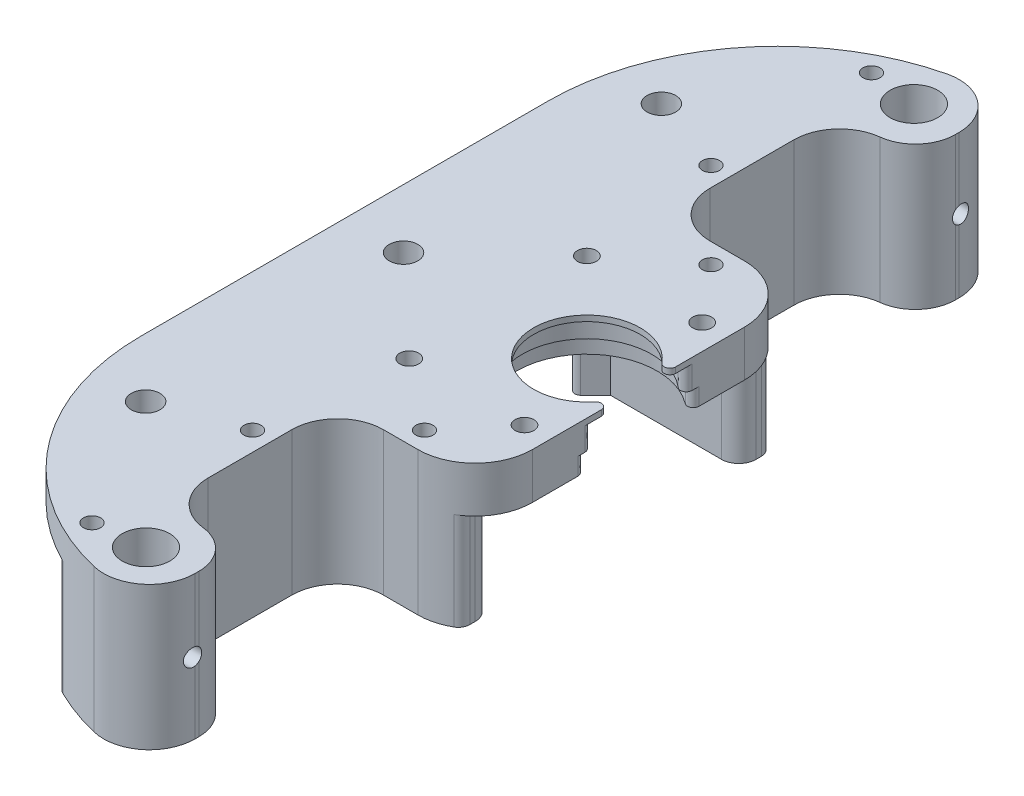
SolidWorks part; units mm, degrees
material "ABS"
ref_plane "Płaszczyzna przednia" through (0, 0, 0) normal (0, 0, 1) x (1, 0, 0)
ref_plane "Płaszczyzna górna" through (0, 0, 0) normal (0, 1, 0) x (1, 0, 0)
ref_plane "Płaszczyzna prawa" through (0, 0, 0) normal (1, 0, 0) x (0, 0, -1)
sketch "Szkic2" plane through (0, 0, 0) normal (0, 1, 0) x (1, 0, 0)
  line L0 (-29.6604, 52.1749) -> (-33.4767, 55.9912) construction
  line L1 (-33.4767, 55.9912) -> (-67.8442, 55.9912) construction
  line L2 (-67.8442, 55.9912) -> (-71.6604, 52.1749) construction
  line L3 (-71.6604, 52.1749) -> (-71.6604, 17.8074) construction
  line L4 (-71.6604, 17.8074) -> (-67.8442, 13.9912) construction
  line L5 (-67.8442, 13.9912) -> (-33.4767, 13.9912) construction
  line L6 (-33.4767, 13.9912) -> (-29.6604, 17.8074) construction
  line L7 (-29.6604, 17.8074) -> (-29.6604, 52.1749) construction
  line L8 (-50.6604, 34.9912) -> (-92.6604, 34.9912) construction
  line L9 (-72.3604, -11.5088) -> (-92.9604, -11.5088) construction
  line L10 (-65.6604, 13.4912) -> (-33.2696, 13.4912)
  line L11 (-33.2696, 13.4912) -> (-29.1604, 17.6003) construction
  line L12 (-29.1604, 17.6003) -> (-29.1604, 52.382)
  line L13 (-29.1604, 52.382) -> (-33.2696, 56.4912) construction
  line L14 (-33.2696, 56.4912) -> (-65.6604, 56.4912)
  line L15 (-65.6604, 81.4912) -> (-33.2696, 56.4912)
  line L16 (-72.3604, 17.8003) -> (-72.3604, -11.5088)
  line L17 (-92.9604, -11.5088) -> (-92.9604, 81.4912)
  line L18 (-69.0104, 109.9912) -> (-69.0104, 102.9912) construction
  line L19 (-65.6604, -11.5088) -> (-65.6604, 13.4912)
  line L20 (-65.6604, -11.5088) -> (-33.2696, 13.4912)
  line L21 (-33.2696, 13.4912) -> (-29.1604, 13.4912)
  line L22 (-29.1604, 13.4912) -> (-29.1604, 17.6003)
  line L23 (-29.1604, 52.382) -> (-29.1604, 56.4912)
  line L24 (-29.1604, 56.4912) -> (-33.2696, 56.4912)
  line L25 (-68.0513, 13.4912) -> (-72.3604, 17.8003)
  line L26 (-68.0513, 56.4912) -> (-72.3604, 52.182)
  line L27 (-65.6604, 81.4912) -> (-65.6604, 56.4912)
  line L28 (-92.9604, 81.4912) -> (-92.9604, 109.9912)
  line L29 (-72.3604, 52.182) -> (-72.3604, 81.4912)
  line L30 (-72.3604, 81.4912) -> (-92.9604, 81.4912) construction
  line L31 (-65.6604, 13.4912) -> (-68.0513, 13.4912)
  line L32 (-68.0513, 56.4912) -> (-65.6604, 56.4912)
  line L33 (-82.6604, -11.5088) -> (-82.6604, 81.4912) construction
  line L34 (-65.6604, 13.4912) -> (-65.6604, 6.4912)
  line L35 (-65.6604, 6.4912) -> (-45.6604, 6.4912)
  line L36 (-45.6604, 6.4912) -> (-45.6604, 13.4912)
  line L37 (-45.6604, 13.4912) -> (-65.6604, 13.4912)
  line L38 (-65.6604, 63.4912) -> (-45.6604, 63.4912)
  line L39 (-45.6604, 63.4912) -> (-45.6604, 56.4912)
  line L40 (-65.6604, 56.4912) -> (-65.6604, 63.4912)
  line L41 (-45.6604, 56.4912) -> (-65.6604, 56.4912)
  line L42 (-92.9604, 109.9912) -> (-72.3604, 109.9912)
  line L43 (-92.9604, -11.5088) -> (-92.9604, -40.0088)
  line L44 (-65.6604, 81.4912) -> (-65.6604, 109.9912)
  line L45 (-69.0104, -40.0088) -> (-69.0104, 109.9912) construction
  line L46 (-45.6604, 9.9912) -> (-72.3604, 9.9912) construction
  line L47 (-45.6604, 59.9912) -> (-72.3604, 59.9912) construction
  line L48 (-72.3604, 109.9912) -> (-52.3604, 109.9912)
  line L49 (-52.3604, -40.0088) -> (-52.3604, 13.4912)
  line L50 (-72.3604, -40.0088) -> (-52.3604, -40.0088)
  line L51 (-72.3604, 109.9912) -> (-72.3604, -40.0088)
  line L52 (-65.6604, 109.9912) -> (-72.3604, 109.9912)
  line L53 (-72.3604, -11.5088) -> (-72.3604, -40.0088)
  line L54 (-65.6604, -40.0088) -> (-65.6604, -11.5088)
  line L55 (-92.9604, -40.0088) -> (-72.3604, -40.0088)
  line L56 (-52.3604, 56.4912) -> (-52.3604, 109.9912)
  circle A0 centre (-50.6604, 34.9912) radius 11.75 construction
  circle A1 centre (-66.1604, 50.4912) radius 1.5 construction
  circle A2 centre (-35.1604, 50.4912) radius 1.5 construction
  circle A3 centre (-35.1604, 19.4912) radius 1.5 construction
  circle A4 centre (-66.1604, 19.4912) radius 1.5 construction
  circle A5 centre (-50.6604, 34.9912) radius 4 construction
  circle A6 centre (-50.6604, 34.9912) radius 11 construction
  circle A7 centre (-82.6604, 34.9912) radius 2.5
  circle A8 centre (-82.6604, -10.0088) radius 2.5
  circle A9 centre (-82.6604, 79.9912) radius 2.5
  circle A10 centre (-50.6604, 34.9912) radius 12.25 construction
  circle A11 centre (-66.1604, 19.4912) radius 1.65
  circle A12 centre (-66.1604, 50.4912) radius 1.65
  circle A13 centre (-35.1604, 50.4912) radius 1.65
  circle A14 centre (-35.1604, 19.4912) radius 1.65
  circle A15 centre (-69.0104, 9.9912) radius 1.5 construction
  circle A16 centre (-69.0104, 102.9912) radius 1.5
  circle A17 centre (-69.0104, -33.0088) radius 1.5
  circle A18 centre (-46.0512, 19.4912) radius 1.65
  circle A19 centre (-46.0512, 50.4912) radius 1.65
  circle A23 centre (-54.0104, 9.9912) radius 1.5
  circle A24 centre (-69.0104, -5.0088) radius 1.5
  circle A25 centre (-54.0104, 59.9912) radius 1.5
  circle A26 centre (-69.0104, 74.9912) radius 1.5
  circle A27 centre (-69.0104, 59.9912) radius 1.5 construction
  circle A28 centre (-50.6604, 34.9912) radius 11.3
  circle A29 centre (-60.5945, -32.0088) radius 4.15
  circle A30 centre (-60.5945, 101.9912) radius 4.15
  point P40 (-92.9604, 34.9912)
  point P66 (-92.9604, 34.9912)
  dimension "D1" = 45
  dimension "D2" = 7
extrude "Dodanie-wyciągnięcie1" add sketch "Szkic2" along normal blind 5 contours L26 L51 L25 L31 L10 L37 L21 L22 L12 L23 L24 L14 L41 L32 A28 A14 A13 A12 A11 | L43 L55 L51 L16 L29 L42 L28 L17 A8 A9 | L50 L54 L19 L31 L25 L16 L51 A24 | L35 L49 L10 L19 A23 | L49 L35 L36 L37 | L20 L49 L35 L19 | L54 L50 L49 L20 A29 | L49 L20 L10 L36 L35 | L48 L51 L29 L26 L32 L27 L44 A16 A26 | L38 L56 L15 L27 | L15 L56 L48 L44 A30 | L41 L56 L38 L27 A25 | L56 L14 L39 L38 | L56 L38 L39 L14 L15 region at (-66.8559, 0, -14.1007) region at (-59.4213, 0, -9.9912) region at (-69.0607, 0, 12.2889) region at (-49.0104, 0, -9.9912) region at (-59.8946, 0, 0.2837) region at (-44.4892, 0, -7.8734) region at (-58.4076, 0, 21.8309) region at (-73.8745, 0, -3.1457) region at (-69.0607, 0, -82.2712) region at (-59.4213, 0, -59.9912) region at (-49.0104, 0, -59.9912) region at (-59.8946, 0, -70.2661) region at (-58.4076, 0, -91.8132) region at (-44.4892, 0, -62.1089)
extrude "Dodanie-wyciągnięcie2" add sketch "Szkic2<3>" against normal blind 20 contours L49 L35 L36 L37 | L35 L49 L10 L19 A23 | L50 L54 L19 L31 L25 L16 L51 A24 | L48 L51 L29 L26 L32 L27 L44 A16 A26 | L41 L56 L38 L27 A25 | L56 L14 L39 L38 region at (-59.4213, 0, -9.9912) region at (-69.0607, 0, 12.2889) region at (-49.0104, 0, -9.9912) region at (-69.0607, 0, -82.2712) region at (-59.4213, 0, -59.9912) region at (-49.0104, 0, -59.9912)
sketch "Szkic2<3>" plane through (0, 0, 0) normal (0, 1, 0) x (1, 0, 0) same geometry as "Szkic2"
fillet "Zaokrąglenie1" radius 7 2 edges at (-52.3604, 2.5, -109.9912) (-52.3604, 2.5, 40.0088)
sketch "Szkic3" plane through (0, 0, 0) normal (0, -1, 0) x (1, 0, 0)
  line L0 (-65.6604, -109.9912) -> (-59.3604, -109.9912) construction
  line L1 (-65.6604, 40.0088) -> (-59.3604, 40.0088) construction
  line L2 (-65.6604, -109.9912) -> (-59.3604, -109.9912)
  line L3 (-65.6604, 40.0088) -> (-59.3604, 40.0088)
  line L4 (-65.6604, 24.0088) -> (-59.3604, 24.0088)
  line L5 (-56.4445, 32.0088) -> (-64.7445, 32.0088) construction
  line L6 (-56.4445, -101.9912) -> (-64.7445, -101.9912) construction
  line L7 (-65.6604, -93.9912) -> (-59.3604, -93.9912)
  line L8 (-52.3604, 33.0088) -> (-52.3604, 31.0088)
  line L9 (-65.6604, 40.0088) -> (-65.6604, 24.0088)
  line L10 (-52.3604, -100.9912) -> (-52.3604, -102.9912)
  line L11 (-65.6604, -93.9912) -> (-65.6604, -109.9912)
  arc A0 (-59.3604, -109.9912) -> (-52.3604, -102.9912) centre (-59.3604, -102.9912) ccw construction
  arc A1 (-52.3604, 33.0088) -> (-59.3604, 40.0088) centre (-59.3604, 33.0088) ccw construction
  arc A2 (-59.3604, -109.9912) -> (-52.3604, -102.9912) centre (-59.3604, -102.9912) ccw
  arc A3 (-52.3604, 33.0088) -> (-59.3604, 40.0088) centre (-59.3604, 33.0088) ccw
  circle A4 centre (-60.5945, 32.0088) radius 4.15 construction
  circle A5 centre (-60.5945, -101.9912) radius 4.15 construction
  arc A6 (-52.3604, 31.0088) -> (-59.3604, 24.0088) centre (-59.3604, 31.0088) cw
  arc A7 (-59.3604, -93.9912) -> (-52.3604, -100.9912) centre (-59.3604, -100.9912) cw
  circle A8 centre (-60.5945, 32.0088) radius 4.15
  circle A9 centre (-60.5945, -101.9912) radius 4.15
extrude "Dodanie-wyciągnięcie3" add sketch "Szkic3" along normal up to surface (20 mm away) up to face at (-62.202, -20, 3.1789)
fillet "Zaokrąglenie2" radius 3 4 edges at (-45.6604, -10, -63.4912) (-45.6604, -10, -56.4912) (-45.6604, -10, -13.4912) (-45.6604, -10, -6.4912)
fillet "Zaokrąglenie3" radius 10 2 edges at (-33.2696, 2.5, -56.4912) (-33.2696, 2.5, -13.4912)
sketch "Szkic4" plane through (0, 0, 0) normal (0, -1, 0) x (1, 0, 0)
  line L1 (-52.3604, 31.0088) -> (-52.3604, 1.2436) construction
  line L4 (-65.6604, -6.4912) -> (-48.6604, -6.4912) construction
  line L5 (-52.3604, 31.0088) -> (-52.3604, 1.2436)
  line L6 (-65.6604, 24.0088) -> (-65.6604, -6.4912) construction
  line L7 (-65.6604, 24.0088) -> (-59.3604, 24.0088) construction
  line L8 (-52.3604, -71.2259) -> (-52.3604, -100.9912) construction
  line L9 (-59.3604, -93.9912) -> (-65.6604, -93.9912) construction
  line L12 (-52.3604, -71.2259) -> (-52.3604, -100.9912)
  line L13 (-59.3604, -93.9912) -> (-65.6604, -93.9912)
  line L14 (-65.6604, -63.4912) -> (-48.6604, -63.4912) construction
  line L15 (-65.6604, -93.9912) -> (-65.6604, -63.4912) construction
  line L16 (-48.6604, -63.4912) -> (-42.339, -63.4912)
  line L17 (-52.3604, -71.2259) -> (-35.9693, -58.5749) construction
  line L18 (-42.339, -63.4912) -> (-52.3604, -71.2259)
  line L19 (-48.6604, -6.4912) -> (-42.339, -6.4912)
  line L20 (-52.3604, 1.2436) -> (-35.9693, -11.4075) construction
  line L21 (-42.339, -6.4912) -> (-52.3604, 1.2436)
  line L22 (-65.6604, -93.9912) -> (-65.6604, -63.4912)
  line L23 (-65.6604, -63.4912) -> (-48.6604, -63.4912)
  line L24 (-65.6604, 24.0088) -> (-59.3604, 24.0088)
  line L25 (-65.6604, 24.0088) -> (-65.6604, -6.4912)
  line L26 (-65.6604, -6.4912) -> (-48.6604, -6.4912)
  arc A2 (-59.3604, 24.0088) -> (-52.3604, 31.0088) centre (-59.3604, 31.0088) ccw construction
  arc A5 (-59.3604, 24.0088) -> (-52.3604, 31.0088) centre (-59.3604, 31.0088) ccw
  arc A6 (-52.3604, -100.9912) -> (-59.3604, -93.9912) centre (-59.3604, -100.9912) ccw construction
  arc A9 (-52.3604, -100.9912) -> (-59.3604, -93.9912) centre (-59.3604, -100.9912) ccw
extrude "Wytnij-wyciągnięcie1" cut sketch "Szkic4" against normal through all
fillet "Zaokrąglenie4" radius 15 4 edges at (-29.1604, 2.5, -56.4912) (-29.1604, 2.5, -13.4912) (-42.339, 2.5, -63.4912) (-42.339, 2.5, -6.4912)
fillet "Zaokrąglenie5" radius 1 2 edges at (-72.3604, -10, -52.182) (-72.3604, -10, -17.8003)
fillet "Zaokrąglenie6" radius 40 2 edges at (-92.9604, 2.5, -109.9912) (-92.9604, 2.5, 40.0088)
fillet "Zaokrąglenie7" radius 3 2 edges at (-72.3604, -10, -105.4871) (-72.3604, -10, 35.5047)
fillet "Zaokrąglenie10" radius 8 2 edges at (-59.3604, -7.5, -109.9912) (-59.3604, -7.5, 40.0088)
fillet "Zaokrąglenie11" radius 8 4 edges at (-65.6604, -7.5, 24.0088) (-65.6604, -7.5, -93.9912) (-65.6604, -7.5, -63.4912) (-65.6604, -7.5, -6.4912)
sketch "Szkic6" plane through (0, 5, 0) normal (0, 1, 0) x (1, 0, 0)
  circle A0 centre (-50.6604, 34.9912) radius 11.3 construction
  circle A1 centre (-50.6604, 34.9912) radius 11.3
  circle A2 centre (-50.6604, 34.9912) radius 9.3
  dimension "D1" = 2
extrude "Dodanie-wyciągnięcie4" add sketch "Szkic6" against normal blind 1
sketch "Szkic7" plane through (0, 0, 0) normal (0, -1, 0) x (1, 0, 0)
  line L0 (-72.3604, -15.3861) -> (-72.3604, -54.5963)
  line L14 (-92.9604, 0.5241) -> (-92.9604, -70.5065)
  line L15 (-72.3604, -103.6733) -> (-72.3604, -54.5963)
  line L16 (-70.6533, -53.8892) -> (-68.0513, -56.4912)
  line L17 (-68.0513, -56.4912) -> (-48.6604, -56.4912)
  line L18 (-45.6604, -59.4912) -> (-45.6604, -60.4912)
  line L19 (-48.6604, -63.4912) -> (-47.4545, -63.4912)
  line L20 (-38.2895, -60.3656) -> (-35.9693, -58.5749)
  line L21 (-29.1604, -45.9856) -> (-29.1604, -23.9967)
  line L22 (-35.9693, -11.4075) -> (-38.2895, -9.6167)
  line L23 (-47.4545, -6.4912) -> (-48.6604, -6.4912)
  line L24 (-45.6604, -9.4912) -> (-45.6604, -10.4912)
  line L25 (-48.6604, -13.4912) -> (-68.0513, -13.4912)
  line L26 (-68.0513, -13.4912) -> (-70.6533, -16.0932)
  line L27 (-72.3604, -15.3861) -> (-72.3604, 33.691)
  line L30 (-70.6533, -53.8892) -> (-68.0513, -56.4912)
  line L31 (-68.0513, -56.4912) -> (-48.6604, -56.4912)
  line L32 (-45.6604, -59.4912) -> (-45.6604, -60.4912)
  line L33 (-48.6604, -63.4912) -> (-47.4545, -63.4912)
  line L34 (-38.2895, -60.3656) -> (-35.9693, -58.5749)
  line L35 (-29.1604, -45.9856) -> (-29.1604, -23.9967)
  line L36 (-35.9693, -11.4075) -> (-38.2895, -9.6167)
  line L37 (-47.4545, -6.4912) -> (-48.6604, -6.4912)
  line L38 (-45.6604, -9.4912) -> (-45.6604, -10.4912)
  line L39 (-48.6604, -13.4912) -> (-68.0513, -13.4912)
  line L40 (-68.0513, -13.4912) -> (-70.6533, -16.0932)
  circle A0 centre (-50.6604, -34.9912) radius 12.25
  circle A1 centre (-66.1604, -19.4912) radius 1.65 construction
  circle A2 centre (-66.1604, -50.4912) radius 1.65 construction
  circle A3 centre (-35.1604, -50.4912) radius 1.65 construction
  circle A4 centre (-35.1604, -19.4912) radius 1.65 construction
  circle A5 centre (-66.1604, -19.4912) radius 1.65
  circle A6 centre (-66.1604, -50.4912) radius 1.65
  circle A7 centre (-35.1604, -50.4912) radius 1.65
  circle A8 centre (-35.1604, -19.4912) radius 1.65
  circle A9 centre (-46.0512, -19.4912) radius 1.65 construction
  circle A10 centre (-46.0512, -50.4912) radius 1.65 construction
  circle A11 centre (-46.0512, -19.4912) radius 1.65
  circle A12 centre (-46.0512, -50.4912) radius 1.65
  arc A25 (-92.9604, -70.5065) -> (-70.6902, -106.3625) centre (-52.9604, -70.5065) ccw
  arc A26 (-72.3604, -103.6733) -> (-70.6902, -106.3625) centre (-69.3604, -103.6733) ccw
  arc A27 (-70.6533, -53.8892) -> (-72.3604, -54.5963) centre (-71.3604, -54.5963) ccw
  arc A28 (-45.6604, -59.4912) -> (-48.6604, -56.4912) centre (-48.6604, -59.4912) ccw
  arc A29 (-48.6604, -63.4912) -> (-45.6604, -60.4912) centre (-48.6604, -60.4912) ccw
  arc A30 (-47.4545, -63.4912) -> (-38.2895, -60.3656) centre (-47.4545, -48.4912) ccw
  arc A31 (-35.5797, -58.289) -> (-35.9693, -58.5749) centre (-29.8593, -66.4912) ccw
  arc A32 (-35.5797, -58.289) -> (-29.1604, -45.9856) centre (-44.1604, -45.9856) ccw
  arc A33 (-29.1604, -23.9967) -> (-35.5797, -11.6934) centre (-44.1604, -23.9967) ccw
  arc A34 (-35.9693, -11.4075) -> (-35.5797, -11.6934) centre (-29.8593, -3.4912) ccw
  arc A35 (-38.2895, -9.6167) -> (-47.4545, -6.4912) centre (-47.4545, -21.4912) ccw
  arc A36 (-45.6604, -9.4912) -> (-48.6604, -6.4912) centre (-48.6604, -9.4912) ccw
  arc A37 (-48.6604, -13.4912) -> (-45.6604, -10.4912) centre (-48.6604, -10.4912) ccw
  arc A38 (-72.3604, -15.3861) -> (-70.6533, -16.0932) centre (-71.3604, -15.3861) ccw
  arc A39 (-70.6902, 36.3802) -> (-72.3604, 33.691) centre (-69.3604, 33.691) ccw
  arc A40 (-70.6902, 36.3802) -> (-92.9604, 0.5241) centre (-52.9604, 0.5241) ccw
  arc A43 (-70.6533, -53.8892) -> (-72.3604, -54.5963) centre (-71.3604, -54.5963) ccw
  arc A44 (-45.6604, -59.4912) -> (-48.6604, -56.4912) centre (-48.6604, -59.4912) ccw
  arc A45 (-48.6604, -63.4912) -> (-45.6604, -60.4912) centre (-48.6604, -60.4912) ccw
  arc A46 (-47.4545, -63.4912) -> (-38.2895, -60.3656) centre (-47.4545, -48.4912) ccw
  arc A47 (-35.5797, -58.289) -> (-35.9693, -58.5749) centre (-29.8593, -66.4912) ccw
  arc A48 (-35.5797, -58.289) -> (-29.1604, -45.9856) centre (-44.1604, -45.9856) ccw
  arc A49 (-29.1604, -23.9967) -> (-35.5797, -11.6934) centre (-44.1604, -23.9967) ccw
  arc A50 (-35.9693, -11.4075) -> (-35.5797, -11.6934) centre (-29.8593, -3.4912) ccw
  arc A51 (-38.2895, -9.6167) -> (-47.4545, -6.4912) centre (-47.4545, -21.4912) ccw
  arc A52 (-45.6604, -9.4912) -> (-48.6604, -6.4912) centre (-48.6604, -9.4912) ccw
  arc A53 (-48.6604, -13.4912) -> (-45.6604, -10.4912) centre (-48.6604, -10.4912) ccw
  arc A54 (-72.3604, -15.3861) -> (-70.6533, -16.0932) centre (-71.3604, -15.3861) ccw
  dimension "D1" = 0
extrude "Dodanie-wyciągnięcie5" add sketch "Szkic7" along normal blind 3
sketch "Szkic9" plane through (-52.3604, 0, 0) normal (1, 0, 0) x (0, 0, -1)
  line L0 (-36.1588, -20) -> (-27.8588, -20) construction
  line L1 (-36.1588, -20) -> (-27.8588, -20) construction
  line L2 (-27.8588, 5) -> (-36.1588, 5) construction
  line L3 (-27.8588, 5) -> (-36.1588, 5) construction
  line L4 (97.8412, -20) -> (106.1412, -20) construction
  line L5 (106.1412, 5) -> (97.8412, 5) construction
  line L6 (97.8412, -20) -> (106.1412, -20) construction
  line L7 (106.1412, 5) -> (97.8412, 5) construction
  line L8 (101.9912, 5) -> (101.9912, -20) construction
  line L9 (-32.0088, 5) -> (-32.0088, -20) construction
  circle A0 centre (-32.0088, -7.5) radius 1.5
  circle A1 centre (101.9912, -7.5) radius 1.5
extrude "Wytnij-wyciągnięcie4" cut sketch "Szkic9" against normal up to surface (4.3646 mm away) contours A0 up to face at (-60.5945, 5, 36.1588)
extrude "Wytnij-wyciągnięcie5" cut sketch "Szkic9<3>" against normal up to surface (4.3646 mm away) contours A1 up to face at (-60.5945, 5, -97.8412)
sketch "Szkic9<3>" plane through (-52.3604, 0, 0) normal (1, 0, 0) x (0, 0, -1) same geometry as "Szkic9"
sketch "Szkic10" plane through (0, 5, 0) normal (0, 1, 0) x (1, 0, 0)
  line L0 (-41.6604, 54.8881) -> (-41.6604, 73.6881) construction
  line L1 (-66.6604, -16.1055) -> (-66.6604, -1.5088) construction
  line L2 (-57.6604, 7.4912) -> (-47.4545, 7.4912) construction
  line L3 (-38.9005, 10.4083) -> (-36.5803, 12.1991) construction
  line L4 (-30.1604, 23.9967) -> (-30.1604, 45.9856) construction
  line L5 (-36.5803, 57.7832) -> (-38.9005, 59.574) construction
  line L6 (-47.4545, 62.4912) -> (-57.6604, 62.4912) construction
  line L7 (-66.6604, 71.4912) -> (-66.6604, 86.0878) construction
  line L8 (-53.3604, 100.9912) -> (-53.3604, 101.6391) construction
  line L9 (-91.9604, 70.5065) -> (-91.9604, -0.5241) construction
  line L10 (-53.3604, -31.6568) -> (-53.3604, -31.0088) construction
  line L11 (-41.6604, 73.6881) -> (-41.6604, -31.0088)
  line L12 (-41.6604, -31.0088) -> (-3.5798, -31.0088)
  line L13 (-3.5798, -31.0088) -> (-3.5798, 73.6881)
  line L14 (-3.5798, 73.6881) -> (-41.6604, 73.6881)
  arc A0 (-57.6604, 7.4912) -> (-66.6604, -1.5088) centre (-57.6604, -1.5088) ccw construction
  arc A1 (-47.4545, 7.4912) -> (-38.9005, 10.4083) centre (-47.4545, 21.4912) ccw construction
  arc A2 (-36.1518, 12.5136) -> (-36.5803, 12.1991) centre (-29.8593, 3.4912) ccw construction
  arc A3 (-36.1518, 12.5136) -> (-30.1604, 23.9967) centre (-44.1604, 23.9967) ccw construction
  arc A4 (-30.1604, 45.9856) -> (-36.1518, 57.4687) centre (-44.1604, 45.9856) ccw construction
  arc A5 (-36.5803, 57.7832) -> (-36.1518, 57.4687) centre (-29.8593, 66.4912) ccw construction
  arc A6 (-38.9005, 59.574) -> (-47.4545, 62.4912) centre (-47.4545, 48.4912) ccw construction
  arc A7 (-66.6604, 71.4912) -> (-57.6604, 62.4912) centre (-57.6604, 71.4912) ccw construction
  arc A8 (-58.6804, 95.0298) -> (-66.6604, 86.0878) centre (-57.6604, 86.0878) ccw construction
  arc A9 (-58.6804, 95.0298) -> (-53.3604, 100.9912) centre (-59.3604, 100.9912) ccw construction
  arc A10 (-53.3604, 101.6391) -> (-61.9792, 108.4494) centre (-60.3604, 101.6391) ccw construction
  arc A11 (-61.9792, 108.4494) -> (-91.9604, 70.5065) centre (-52.9604, 70.5065) ccw construction
  arc A12 (-91.9604, -0.5241) -> (-61.9792, -38.467) centre (-52.9604, -0.5241) ccw construction
  arc A13 (-61.9792, -38.467) -> (-53.3604, -31.6568) centre (-60.3604, -31.6568) ccw construction
  arc A14 (-53.3604, -31.0088) -> (-58.6804, -25.0475) centre (-59.3604, -31.0088) ccw construction
  arc A15 (-66.6604, -16.1055) -> (-58.6804, -25.0475) centre (-57.6604, -16.1055) ccw construction
extrude "Wytnij-wyciągnięcie6" cut sketch "Szkic10" against normal through all
fillet "Zaokrąglenie12" radius 1 4 edges at (-41.6604, -1.5, -43.3016) (-41.6604, -1.5, -26.6808) (-41.6604, 4.5, -32.6481) (-41.6604, 4.5, -37.3343)
fillet "Zaokrąglenie13" radius 1 2 edges at (-41.6604, 2, -28.1582) (-41.6604, 2, -41.8242)
fillet "Zaokrąglenie14" radius 10 2 edges at (-41.6604, 1, -7.6554) (-41.6604, 1, -62.327)
fillet "Zaokrąglenie15" radius 2 2 edges at (-45.8997, -11.5, -8.3172) (-45.8997, -11.5, -61.6651)
